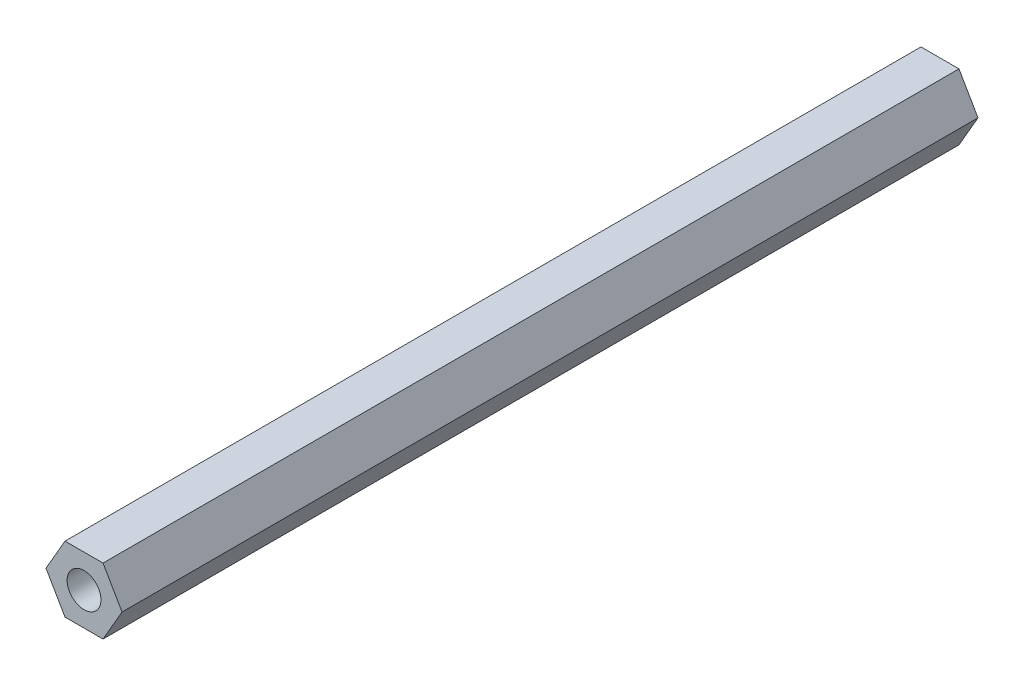
SolidWorks part; units mm, degrees
material "6061-T6 (SS)"
ref_plane "Front Plane" through (0, 0, 0) normal (0, 0, 1) x (1, 0, 0)
ref_plane "Top Plane" through (0, 0, 0) normal (0, 1, 0) x (1, 0, 0)
ref_plane "Right Plane" through (0, 0, 0) normal (1, 0, 0) x (0, 0, -1)
sketch "Sketch1" plane through (0, 0, 0) normal (0, 0, 1) x (1, 0, 0)
  line L1 (-3.6662, 6.35) -> (-7.3323, 0)
  line L2 (-7.3323, 0) -> (-3.6662, -6.35)
  line L3 (-3.6662, -6.35) -> (3.6662, -6.35)
  line L4 (3.6662, -6.35) -> (7.3323, 0)
  line L5 (7.3323, 0) -> (3.6662, 6.35)
  line L6 (3.6662, 6.35) -> (-3.6662, 6.35)
  circle A1 centre (0, 0) radius 3.2639
  circle A2 centre (0, 0) radius 6.35 construction
  dimension "D1" = 6.5278
  dimension "D2" = 12.7
extrude "Boss-Extrude1" add sketch "Sketch1" along normal blind 165.1
